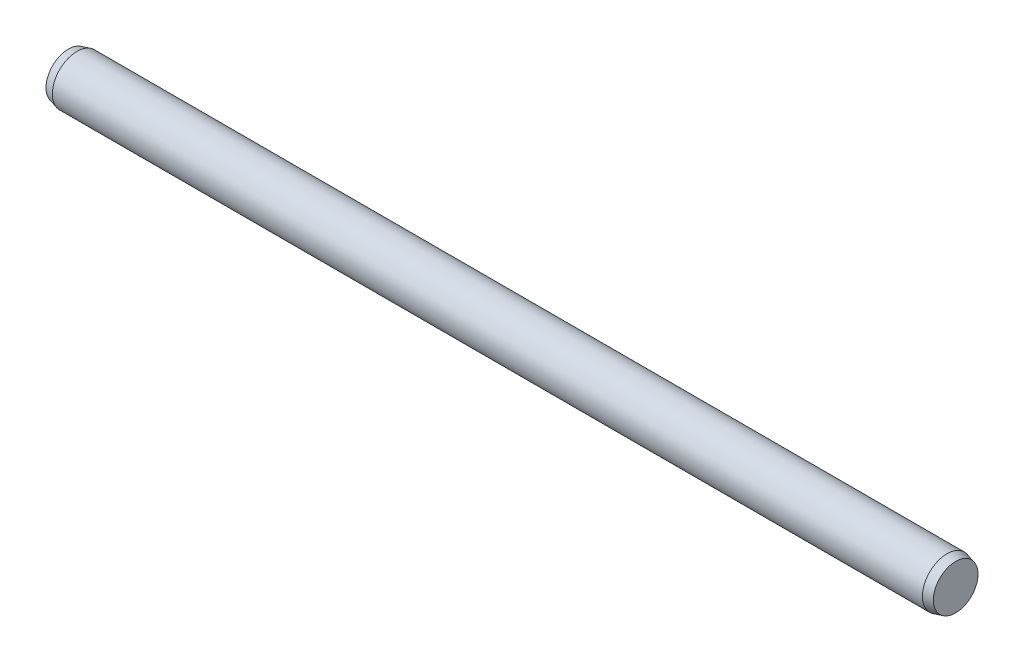
SolidWorks part; units mm, degrees
material "18-8 Stainless Steel"
ref_plane "Front Plane" through (0, 0, 0) normal (0, 0, 1) x (1, 0, 0)
ref_plane "Top Plane" through (0, 0, 0) normal (0, 1, 0) x (1, 0, 0)
ref_plane "Right Plane" through (0, 0, 0) normal (1, 0, 0) x (0, 0, -1)
sketch "Sketch1" plane through (0, 0, 0) normal (0, 0, 1) x (1, 0, 0)
  line L0 (-17.65, 0) -> (17.65, 0) construction
  line L1 (17.65, 1) -> (17.65, -1) construction
  line L2 (-17.65, 1) -> (-17.65, -1) construction
  line L3 (18, 1) -> (18, -1) construction
  line L4 (-18, 1) -> (-18, -1) construction
  line L5 (-17.65, 0) -> (-18, 0) construction
  line L6 (17.65, 0) -> (18, 0) construction
  dimension "Dia" = 2
  dimension "C" = 0.35
  dimension "D1" = 0.35
  dimension "Length" = 36
sketch "Sketch2" plane through (0, 0, 0) normal (1, 0, 0) x (0, 0, -1)
  circle A0 centre (0, 0) radius 1
extrude "Extrude1" add sketch "Sketch2" against normal up to vertex (17.65 mm away) and the other way up to vertex (17.65 mm away) up to point (-17.65, 1, 0) other way up to point (17.65, 1, 0)
sketch "Sketch3" plane through (17.65, 0, 0) normal (1, 0, 0) x (0, 0, -1)
  circle A1 centre (0, 0) radius 1
  circle A2 centre (0, 0) radius 1
  dimension "D1" = 0
extrude "Extrude2" add sketch "Sketch3" along normal up to vertex (0.35 mm away) draft 15 up to point (18, 0, 0)
sketch "Sketch4" plane through (-17.65, 0, 0) normal (-1, 0, 0) x (0, 0, 1)
  circle A1 centre (0, 0) radius 1
  circle A2 centre (0, 0) radius 1
  dimension "D1" = 0
extrude "Extrude3" add sketch "Sketch4" along normal up to vertex (0.35 mm away) draft 15 up to point (-18, 0, 0)
equation "\"D1@Sketch1\" = \"C@Sketch1\""
